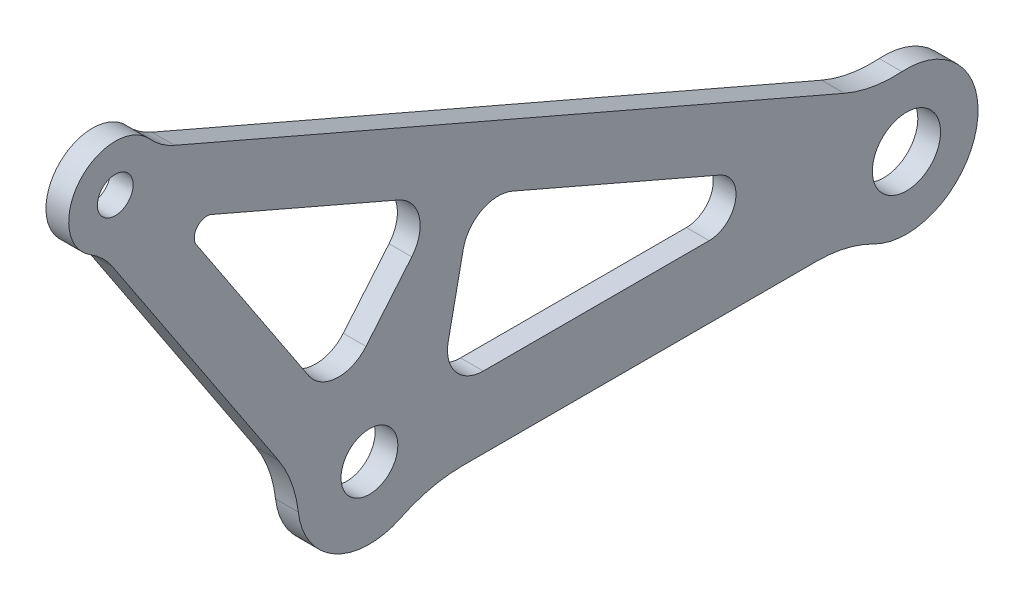
SolidWorks part; units mm, degrees
material "AISI 1020"
ref_plane "Front Plane" through (0, 0, 0) normal (0, 0, 1) x (1, 0, 0)
ref_plane "Top Plane" through (0, 0, 0) normal (0, 1, 0) x (1, 0, 0)
ref_plane "Right Plane" through (0, 0, 0) normal (1, 0, 0) x (0, 0, -1)
sketch "Sketch1" plane through (0, 0, 0) normal (1, 0, 0) x (0, 0, -1)
  line L0 (-60.7171, 0) -> (60.7171, 0)
  line L3 (0, -143.7223) -> (0, 143.7223) construction
  line L4 (-149.7529, 101.5535) -> (-94.5581, 18.1812)
  line L5 (-134.4049, 119.8783) -> (67.4524, 32.5212)
  line L6 (-75, 14) -> (75, 14) construction
  line L8 (-146, 114) -> (-75, 14) construction
  arc A20 (-134.4049, 119.8783) -> (-149.7529, 101.5535) centre (-146, 114) ccw
  arc A22 (-94.5581, 18.1812) -> (-60.7171, 0) centre (-75, 14) ccw
  arc A23 (60.7171, 0) -> (67.4524, 32.5212) centre (75, 14) ccw
  point P5 (0, 0)
  point P14 (0, 0)
  dimension "D3" = 20
  dimension "D5" = 13
  dimension "D6" = 20
  dimension "D4" = 127
  dimension "D7" = 254
  dimension "D10" = 6
  dimension "D11" = 6
  dimension "D9" = 3
  dimension "D12" = 3
  dimension "D13" = 6
  dimension "D14" = 6
  dimension "D2" = 150
  dimension "D8" = 122.6418
extrude "Boss-Extrude1" add sketch "Sketch1" along normal blind 6.35
hole_wizard "3/4 (0.75) Diameter Hole1" positions "Sketch4" profile "Sketch3" hole size "3/4" standard "ANSI Inch" end condition up to next
sketch "Sketch4" plane through (6.35, 0, 0) normal (1, 0, 0) x (0, 0, -1)
  point P5 (75, 14)
sketch "Sketch3" plane through (6.35, 14, -75) normal (0, 1, 0) x (0, 0, -1)
  line L0 (0, 0) -> (0, 6.35)
  line L1 (0, 6.35) -> (9.525, 6.35)
  line L2 (9.525, 6.35) -> (9.525, 0)
  line L5 (9.525, 0) -> (0, 0)
  line L11 (0, -6.35) -> (0, 107.95) construction
  dimension "Thru Hole Dia." = 19.05
  dimension "Thru Hole Depth" = 6.35
hole_wizard "Ø10.0 (10) Diameter Hole1" positions "Sketch9" profile "Sketch6" hole size "Ø10.0" standard "ANSI Metric" end condition up to next
sketch "Sketch9" plane through (6.35, 0, 0) normal (1, 0, 0) x (0, 0, -1)
  point P0 (-146, 114)
sketch "Sketch6" plane through (6.35, 114, 146) normal (0, 1, 0) x (0, 0, -1)
  line L0 (0, 0) -> (0, 6.35)
  line L1 (0, 6.35) -> (5, 6.35)
  line L2 (5, 6.35) -> (5, 0)
  line L5 (5, 0) -> (0, 0)
  line L11 (0, -6.35) -> (0, 107.95) construction
  dimension "Thru Hole Dia." = 10
  dimension "Thru Hole Depth" = 6.35
hole_wizard "Ø5/8\" Diameter Hole2" positions "Sketch16" profile "Sketch11" hole size "5/8" standard "ANSI Inch" end condition up to next
sketch "Sketch16" plane through (6.35, 0, 0) normal (1, 0, 0) x (0, 0, -1)
  line L0 (75, 14) -> (157.5513, 156.983)
  line L2 (0, 0) -> (0, 108.153) construction
  line L4 (-146, 114) -> (-119.4521, 194.8786)
  line L6 (-174.545, 70.324) -> (-178.0536, 59.6351) construction
  line L7 (-174.545, 70.324) -> (-178.0536, 59.6351) construction
  arc A0 (-94.5581, 18.1812) -> (-60.7171, 0) centre (-75, 14) ccw construction
  point P0 (-75, 14)
  point P23 (0, 0)
  dimension "D1" = 30
sketch "Sketch11" plane through (6.35, 14, 75) normal (0, 1, 0) x (0, 0, -1)
  line L0 (0, 0) -> (0, 6.35)
  line L1 (0, 6.35) -> (7.9375, 6.35)
  line L2 (7.9375, 6.35) -> (7.9375, 0)
  line L5 (7.9375, 0) -> (0, 0)
  line L11 (0, -6.35) -> (0, 107.95) construction
  dimension "Thru Hole Dia." = 15.875
  dimension "Thru Hole Depth" = 6.35
sketch "Sketch8" plane through (6.35, 0, 0) normal (1, 0, 0) x (0, 0, -1)
  line L2 (-54.5605, 67.8903) -> (-46.3008, 64.3157) construction
  line L3 (-52.9877, 32.028) -> (-48.7918, 52.2877)
  line L7 (-75.9573, 42.3434) -> (-63.1664, 57.6152)
  line L9 (-123.3455, 90.6494) -> (-91.9619, 43.2441)
  line L10 (-119.037, 95.7935) -> (-66.861, 73.2135)
  line L11 (19.8861, 20) -> (-43.1955, 20)
  line L12 (67.4524, 32.5212) -> (-134.4049, 119.8783) construction
  line L13 (-149.7529, 101.5535) -> (-94.5581, 18.1812) construction
  line L14 (-60.7171, 0) -> (60.7171, 0) construction
  line L15 (-84.5632, 32.0683) -> (-84.2827, 31.6447) construction
  line L16 (-55.4787, 20) -> (-55.9867, 20) construction
  line L17 (-54.5605, 67.8903) -> (-46.3008, 64.3157) construction
  line L18 (-35.0279, 59.4372) -> (22.8649, 34.3831)
  line L19 (-120.4271, 92.5814) -> (-104.3957, 79.1543) construction
  line L20 (19.8861, 27.5) -> (27.9693, 25.826) construction
  line L21 (-29.8567, 10) -> (10.3311, 10) construction
  arc A0 (-52.9877, 32.028) -> (-43.1955, 20) centre (-43.1955, 30) ccw
  arc A2 (-48.7918, 52.2877) -> (-35.0279, 59.4372) centre (-38.9996, 50.2597) cw
  arc A4 (-63.1664, 57.6152) -> (-66.861, 73.2135) centre (-70.8327, 64.0361) ccw
  arc A14 (-119.037, 95.7935) -> (-123.3455, 90.6494) centre (-120.4271, 92.5814) ccw
  arc A20 (-75.9573, 42.3434) -> (-91.9619, 43.2441) centre (-83.6236, 48.7643) cw
  arc A25 (-134.4049, 119.8783) -> (-149.7529, 101.5535) centre (-146, 114) ccw construction
  circle A27 centre (-146, 114) radius 5 construction
  arc A36 (-94.5581, 18.1812) -> (-60.7171, 0) centre (-75, 14) ccw construction
  circle A39 centre (-75, 14) radius 7.9375 construction
  arc A40 (19.8861, 20) -> (22.8649, 34.3831) centre (19.8861, 27.5) ccw
  circle A54 centre (-75, 14) radius 19.9375
  arc A55 (-55.9867, 20) -> (-84.2827, 31.6447) centre (-75, 14) ccw construction
  point P7 (-33.5049, 66.1162)
  point P19 (-33.4763, 76.1997)
  dimension "D8" = 8
  dimension "D9" = 12.0625
  dimension "D11" = 9
  dimension "D7" = 4
  dimension "D1" = 7
  dimension "D10" = 24.8576
  dimension "D2" = 15
  dimension "D12" = 10
  dimension "D13" = 14.6862
  dimension "D3" = 12
  dimension "D5" = 16
  dimension "D6" = 20
  dimension "D4" = 16
extrude "Cut-Extrude1" cut sketch "Sketch8" against normal up to next
fillet "Fillet1" radius 35 1 edges at (3.175, 18.1812, 94.5581)
fillet "Fillet3" radius 35 2 edges at (3.175, 32.5212, -67.4524) (3.175, 0, -60.7171)
fillet "Fillet4" radius 20 2 edges at (3.175, 101.5535, 149.7529) (3.175, 119.8783, 134.4049)
fillet "Fillet6" radius 40 1 edges at (3.175, 0, 60.7171)
equation "\"D11@Sketch1\"=\"D10@Sketch1\""
equation "\"D12@Sketch1\"=\"D9@Sketch1\""
equation "\"D14@Sketch1\"=\"D13@Sketch1\""
